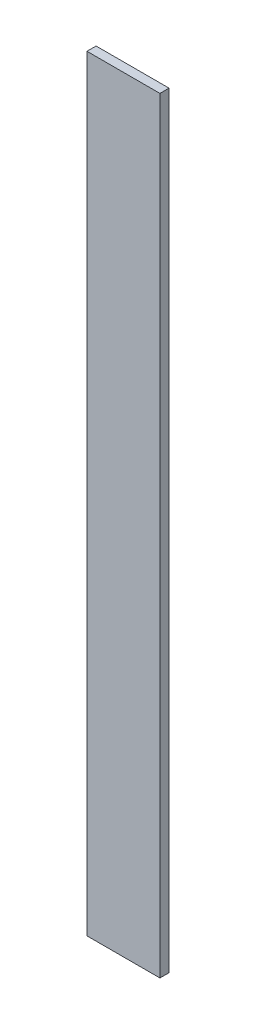
SolidWorks part; units mm, degrees
material "Pin"
ref_plane "Front" through (0, 0, 0) normal (0, 0, 1) x (1, 0, 0)
ref_plane "Top" through (0, 0, 0) normal (0, 1, 0) x (1, 0, 0)
ref_plane "Right" through (0, 0, 0) normal (1, 0, 0) x (0, 0, -1)
sketch "Esquisse1" plane through (0, 0, 0) normal (0, 0, 1) x (1, 0, 0)
  line L1 (-25.4, 266.7) -> (25.4, 266.7)
  line L2 (-25.4, 266.7) -> (-25.4, -266.7)
  line L3 (-25.4, -266.7) -> (25.4, -266.7)
  line L4 (25.4, 266.7) -> (25.4, -266.7)
  line L5 (-25.4, 266.7) -> (25.4, -266.7) construction
  line L6 (-25.4, -266.7) -> (25.4, 266.7) construction
  point P0 (0, 0)
  dimension "D1" = 533.4
  dimension "D2" = 50.8
extrude "Boss.-Extru.1" add sketch "Esquisse1" along normal blind 6.35
